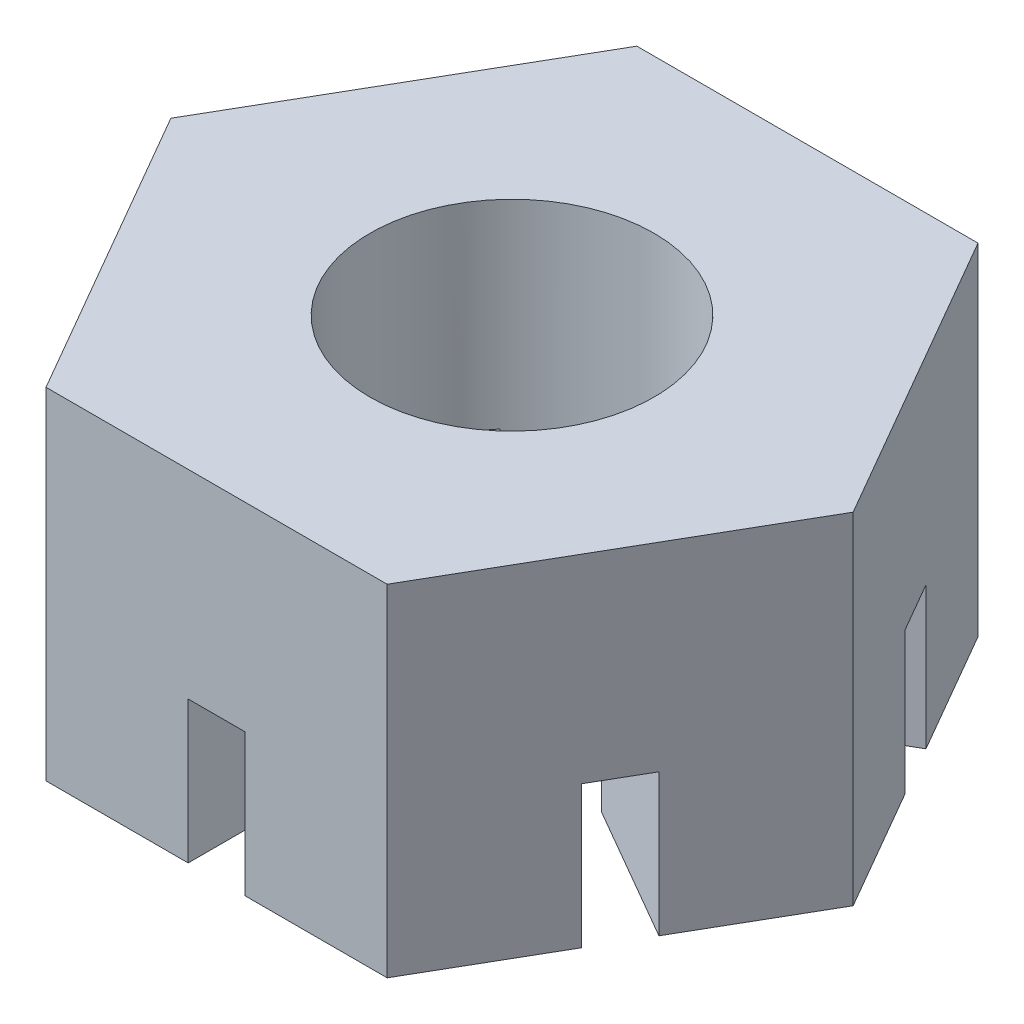
SolidWorks part; units mm, degrees
ref_plane "Front Plane" through (0, 0, 0) normal (0, 0, 1) x (1, 0, 0)
ref_plane "Top Plane" through (0, 0, 0) normal (0, 1, 0) x (1, 0, 0)
ref_plane "Right Plane" through (0, 0, 0) normal (1, 0, 0) x (0, 0, -1)
sketch "Sketch1" plane through (0, 0, 0) normal (0, 1, 0) x (1, 0, 0)
  line L0 (0, 92.2175) -> (0, -91.118) construction
  line L1 (30.0222, -52) -> (60.0444, 0)
  line L2 (60.0444, 0) -> (30.0222, 52)
  line L3 (30.0222, 52) -> (-30.0222, 52)
  line L4 (-30.0222, 52) -> (-60.0444, 0)
  line L5 (-60.0444, 0) -> (-30.0222, -52)
  line L6 (-30.0222, -52) -> (30.0222, -52)
  line L7 (-114.831, 0) -> (127.8755, 0) construction
  line L8 (-5, 52) -> (-5, 24.4949)
  line L9 (5, 52) -> (5, 24.4949)
  line L10 (42.5333, 30.3301) -> (18.7132, 16.5776)
  line L11 (47.5333, 21.6699) -> (23.7132, 7.9173)
  line L12 (47.5333, -21.6699) -> (23.7132, -7.9173)
  line L13 (42.5333, -30.3301) -> (18.7132, -16.5776)
  line L14 (5, -52) -> (5, -24.4949)
  line L15 (-5, -52) -> (-5, -24.4949)
  line L16 (-42.5333, -30.3301) -> (-18.7132, -16.5776)
  line L17 (-47.5333, -21.6699) -> (-23.7132, -7.9173)
  line L18 (-47.5333, 21.6699) -> (-23.7132, 7.9173)
  line L19 (-42.5333, 30.3301) -> (-18.7132, 16.5776)
  circle A0 centre (0, 0) radius 52 construction
  circle A1 centre (0, 0) radius 25
  point P19 (0, 0)
  point P20 (0, 0)
  point P40 (0, 0)
  point P41 (0, 0)
  dimension "D2" = 50
  dimension "D1" = 104
  dimension "D3" = 5
  dimension "D4" = 6
extrude "Boss-Extrude1" add sketch "Sketch1" along normal blind 60 contours A1 L19 L4 L18 | A1 L8 L3 L4 L19 | A1 L9 L3 L8 | A1 L10 L2 L3 L9 | A1 L11 L2 L10 | A1 L12 L1 L2 L11 | A1 L13 L1 L12 | A1 L14 L6 L1 L13 | A1 L15 L6 L14 | A1 L16 L5 L6 L15 | A1 L17 L5 L16 | A1 L18 L4 L5 L17 region at (20.8337, 0, 36.0849) region at (33.269, 0, 19.2079) region at (0, 0, 38.4157) region at (41.6673, 0, 0) region at (-20.8337, 0, 36.0849) region at (33.269, 0, -19.2079) region at (-33.269, 0, 19.2079) region at (20.8337, 0, -36.0849) region at (-41.6673, 0, 0) region at (-33.269, 0, -19.2079) region at (0, 0, -38.4157) region at (-20.8337, 0, -36.0849)
extrude "Cut-Extrude1" cut sketch "Sketch1<4>" along normal blind 25 contours A1 L19 L4 L18 | A1 L17 L5 L16 | A1 L15 L6 L14 | A1 L13 L1 L12 | A1 L11 L2 L10 | A1 L9 L3 L8 region at (33.269, 0, 19.2079) region at (0, 0, 38.4157) region at (33.269, 0, -19.2079) region at (-33.269, 0, 19.2079) region at (-33.269, 0, -19.2079) region at (0, 0, -38.4157)
sketch "Sketch1<4>" plane through (0, 0, 0) normal (0, 1, 0) x (1, 0, 0) same geometry as "Sketch1"
